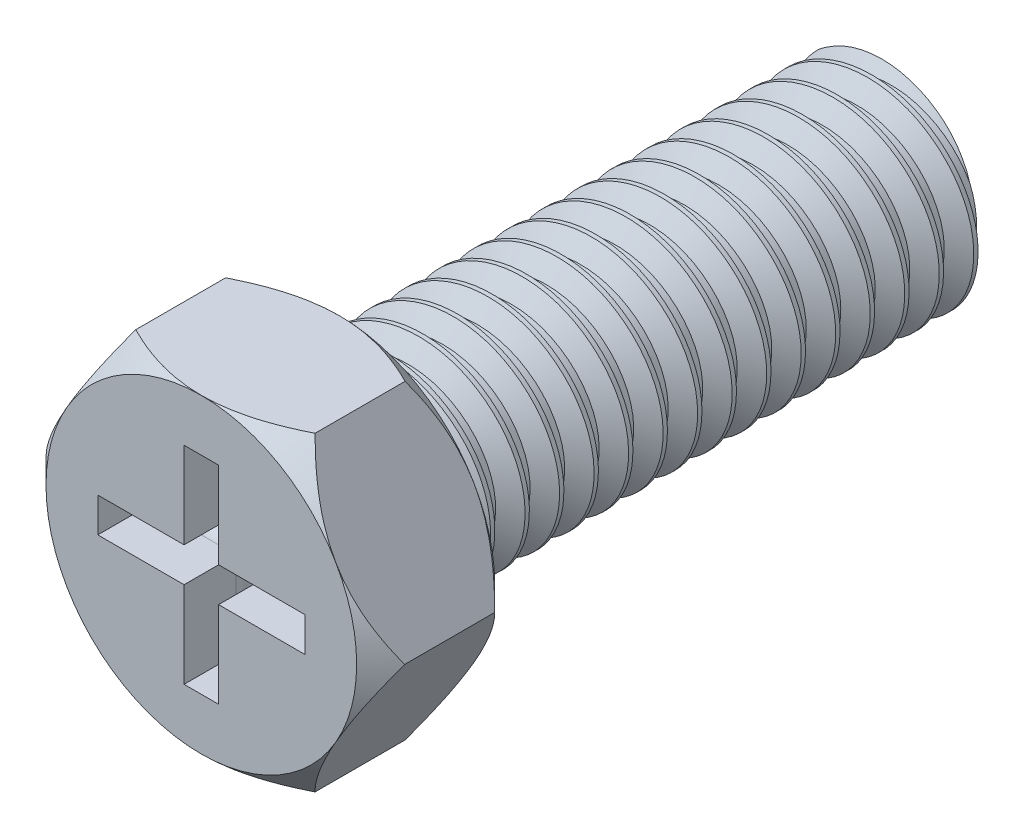
SolidWorks part; units mm, degrees
ref_plane "Front Plane" through (0, 0, 0) normal (0, 0, 1) x (1, 0, 0)
ref_plane "Top Plane" through (0, 0, 0) normal (0, 1, 0) x (1, 0, 0)
ref_plane "Right Plane" through (0, 0, 0) normal (1, 0, 0) x (0, 0, -1)
sketch "Sketch1" plane through (0, 0, 0) normal (0, 0, 1) x (1, 0, 0)
  line L0 (-2.5981, 0) -> (2.5981, 0) construction
  line L1 (2.5981, 0) -> (1.299, 2.25)
  line L2 (1.299, 2.25) -> (-1.299, 2.25)
  line L3 (-1.299, 2.25) -> (-2.5981, 0)
  line L4 (-2.5981, 0) -> (-1.299, -2.25)
  line L5 (-1.299, -2.25) -> (1.299, -2.25)
  line L6 (1.299, -2.25) -> (2.5981, 0)
  line L7 (0, 2.25) -> (0, -2.25) construction
  circle A0 centre (0, 0) radius 2.25
  circle A1 centre (0, 0) radius 1.5
  dimension "D1" = 4.5
  dimension "D2" = 3
extrude "Boss-Extrude1" add sketch "Sketch1" along normal blind 2 contours L1 L2 L3 L4 L5 L6
extrude "Boss-Extrude2" add sketch "Sketch1<3>" along normal up to next (2 mm away) and the other way blind 8 contours A1
sketch "Sketch1<3>" plane through (0, 0, 0) normal (0, 0, 1) x (1, 0, 0) same geometry as "Sketch1"
thread "Thread1" pitch 0.5 method cut profile "Thread Profile2" start angle 0, offset 0, length 0, pitch 0.5, diameter 3
ref_plane "Plane2" through (-1.5, 0, 0) normal (0, -1, 0) x (-1, 0, 0)
sketch "Thread Profile2" plane through (-1.5, 0, 0) normal (0, -1, 0) x (-1, 0, 0)
  line L0 (0, 0) -> (0, 0.5) construction
  line L11 (0, 0) -> (0, 0.4375)
  line L12 (0, 0.4375) -> (-0.2706, 0.2812)
  line L13 (-0.2706, 0.2812) -> (-0.2706, 0.1562)
  line L15 (-0.2706, 0.1562) -> (0, 0)
  line L17 (-0.2706, 0.2187) -> (0, 0.2187) construction
  point P2 (0, 0)
  dimension "Pitch" = 0.5
  dimension "Profile_Angle" = 60
  dimension "Profile_Land" = 0.125
  dimension "Profile_Height" = 0.2706
extrude "Cut-Extrude3" cut sketch "Sketch1<8>" along normal blind 1 draft 45 flip side to cut contours A0
sketch "Sketch1<8>" plane through (0, 0, 0) normal (0, 0, 1) x (1, 0, 0) same geometry as "Sketch1"
ref_plane "Plane3" through (0, 0, 2) normal (0, 0, 1) x (1, 0, 0)
sketch "Sketch8" plane through (0, 0, 2) normal (0, 0, 1) x (1, 0, 0)
  circle A0 centre (0, 0) radius 2.25
  dimension "D1" = 4.5
extrude "Cut-Extrude4" cut sketch "Sketch8" against normal blind 1 draft 45 flip side to cut contours A0
ref_plane "Plane4" through (0, 0, -8) normal (0, 0, -1) x (-1, 0, 0)
sketch "Sketch9" plane through (0, 0, -8) normal (0, 0, -1) x (-1, 0, 0)
  line L0 (-2.5981, 0) -> (2.5981, 0) construction
  line L1 (0, 2.25) -> (0, -2.25) construction
  line L2 (-1.299, 2.25) -> (1.299, 2.25) construction
ref_plane "Plane5" through (0, 0, 2) normal (0, 0, 1) x (1, 0, 0)
sketch "Sketch10" plane through (0, 0, 2) normal (0, 0, 1) x (1, 0, 0)
  line L0 (0, 1.5) -> (0, -1.5) construction
  line L1 (1.5, 0) -> (-1.5, 0) construction
  line L2 (-0.25, -1.5) -> (0.25, -1.5)
  line L3 (0.25, -1.5) -> (0.25, -0.25)
  line L4 (0.25, -0.25) -> (1.5, -0.25)
  line L5 (1.5, -0.25) -> (1.5, 0.25)
  line L6 (1.5, 0.25) -> (0.25, 0.25)
  line L7 (0.25, 0.25) -> (0.25, 1.5)
  line L8 (0.25, 1.5) -> (-0.25, 1.5)
  line L9 (-0.25, 1.5) -> (-0.25, 0.25)
  line L10 (-0.25, 0.25) -> (-1.5, 0.25)
  line L12 (-1.5, 0.25) -> (-1.5, -0.25)
  line L13 (-1.5, -0.25) -> (-0.25, -0.25)
  line L14 (-0.25, -0.25) -> (-0.25, -1.5)
  point P5 (0, 0)
  point P10 (0, 0)
  dimension "D1" = 3
  dimension "D2" = 3
  dimension "D3" = 0.5
  dimension "D4" = 0.5
  dimension "D5" = 0.5
  dimension "D6" = 0.5
  dimension "D7" = 0.5
  dimension "D8" = 1.25
  dimension "D9" = 1.25
  dimension "D10" = 1.25
extrude "Cut-Extrude5" cut sketch "Sketch10" against normal blind 1
fillet "Fillet1" radius 0.25 12 edges at (-0.875, -0.25, 1) (-1.5, 0, 1) (-0.875, 0.25, 1) (-0.25, 0.875, 1) (0, 1.5, 1) (0.25, 0.875, 1) (0.875, 0.25, 1) (1.5, 0, 1) (0.875, -0.25, 1) (0.25, -0.875, 1) (0, -1.5, 1) (-0.25, -0.875, 1)
equation "\"D1@Sketch8\"= \"D1@Sketch1\""
